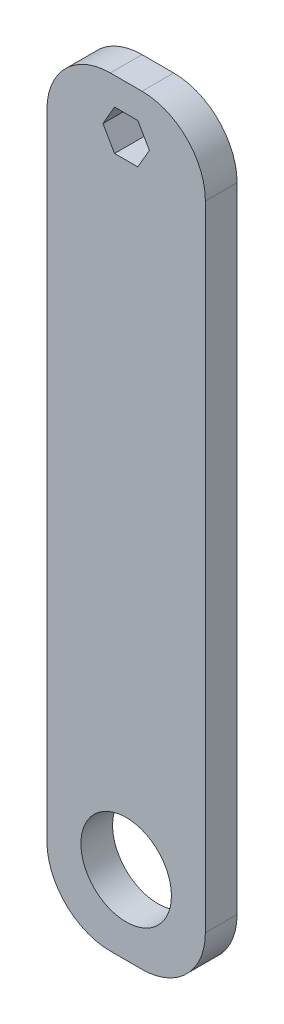
SolidWorks part; units mm, degrees
ref_plane "Front Plane" through (0, 0, 0) normal (0, 0, 1) x (1, 0, 0)
ref_plane "Top Plane" through (0, 0, 0) normal (0, 1, 0) x (1, 0, 0)
ref_plane "Right Plane" through (0, 0, 0) normal (1, 0, 0) x (0, 0, -1)
sketch "Sketch1" plane through (0, 0, 0) normal (0, 1, 0) x (1, 0, 0)
  line L1 (-25, -5) -> (25, -5)
  line L2 (-25, -5) -> (-25, 5)
  line L3 (-25, 5) -> (25, 5)
  line L4 (25, -5) -> (25, 5)
  line L5 (-25, -5) -> (25, 5) construction
  line L6 (-25, 5) -> (25, -5) construction
  point P0 (0, 0)
  dimension "D1" = 50
  dimension "D2" = 10
extrude "Boss-Extrude1" add sketch "Sketch1" along normal mid plane 240
ref_plane "Plane1" through (0, 105, 0) normal (0, 1, 0) x (1, 0, 0)
sketch "Sketch2" plane through (0, 0, 5) normal (0, 0, 1) x (1, 0, 0)
  line L0 (0, -55) -> (0, 55) construction
  line L1 (5.5, 105) -> (-5.5, 105) construction
  line L2 (3.6662, 98.65) -> (7.3323, 105)
  line L3 (7.3323, 105) -> (3.6662, 111.35)
  line L4 (3.6662, 111.35) -> (-3.6662, 111.35)
  line L5 (-3.6662, 111.35) -> (-7.3323, 105)
  line L6 (-7.3323, 105) -> (-3.6662, 98.65)
  line L9 (-3.6662, 98.65) -> (3.6662, 98.65)
  circle A0 centre (0, 105) radius 6.35 construction
  circle A2 centre (0, -95.26) radius 14.2875
  dimension "D1" = 12.7
  dimension "D2" = 200.26
  dimension "D3" = 28.575
extrude "Cut-Extrude1" cut sketch "Sketch2" against normal blind 127
fillet "Fillet1" radius 20 4 edges at (-25, -120, 0) (25, -120, 0) (25, 120, 0) (-25, 120, 0)
ref_axis "Axis1" through (0, -95.26, -5) along (0, 0, 1)
ref_axis "Axis2" through (0, 105, -88.99) along (0, 0, 1)
